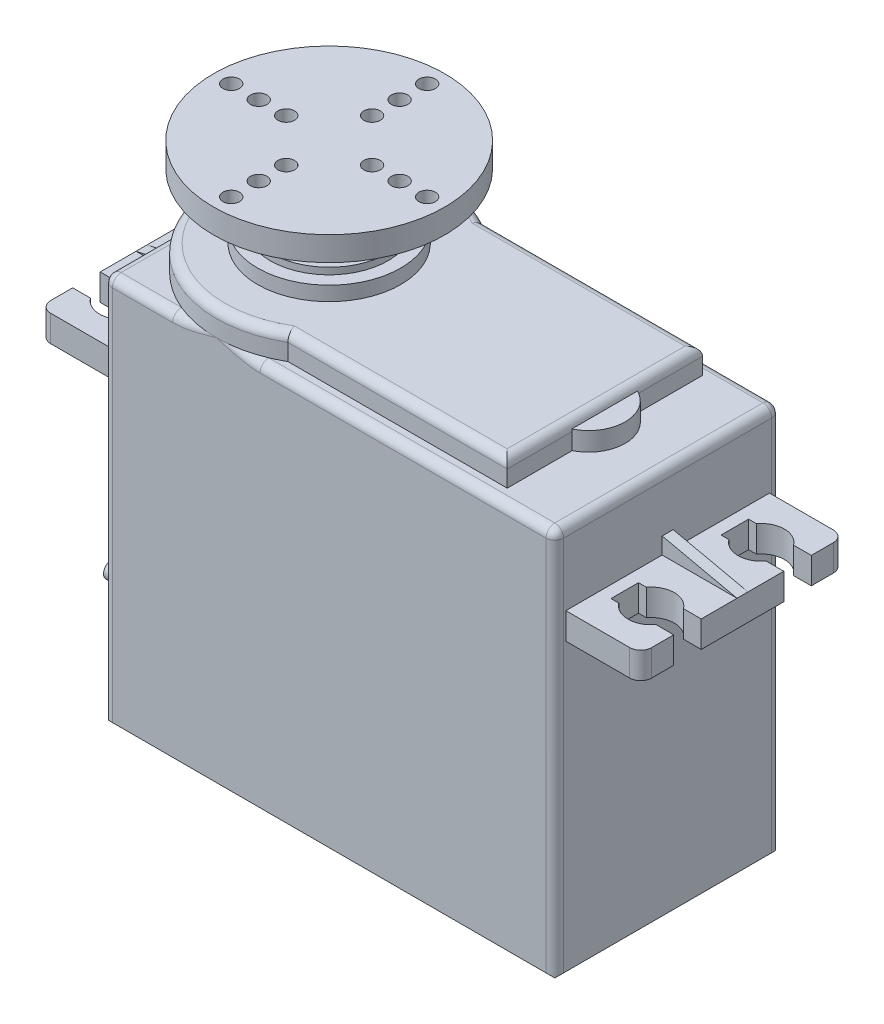
SolidWorks part; units mm, degrees
ref_plane "Front Plane" through (0, 0, 0) normal (0, 0, 1) x (1, 0, 0)
ref_plane "Top Plane" through (0, 0, 0) normal (0, 1, 0) x (1, 0, 0)
ref_plane "Right Plane" through (0, 0, 0) normal (1, 0, 0) x (0, 0, -1)
sketch "Sketch1" plane through (0, 0, 0) normal (0, 1, 0) x (1, 0, 0)
  line L1 (-20.5, 10.25) -> (20.5, 10.25)
  line L2 (-20.5, 10.25) -> (-20.5, -10.25)
  line L3 (-20.5, -10.25) -> (20.5, -10.25)
  line L4 (20.5, 10.25) -> (20.5, -10.25)
  line L5 (-20.5, 10.25) -> (20.5, -10.25) construction
  line L6 (-20.5, -10.25) -> (20.5, 10.25) construction
  point P0 (0, 0)
  dimension "D1" = 41
  dimension "D2" = 20.5
extrude "Boss-Extrude1" add sketch "Sketch1" along normal blind 37
chamfer "Chamfer1" distance 2 angle 45 4 edges at (-20.5, 0, 0) (0, 0, -10.25) (20.5, 0, 0) (0, 0, 10.25)
sketch "Sketch2" plane through (0, 37, 0) normal (0, 1, 0) x (1, 0, 0)
  line L0 (-5.122, 8.875) -> (14.8, 8.875)
  line L1 (14.8, 8.875) -> (14.8, 2.9719)
  line L2 (14.8, -8.875) -> (-5.122, -8.875)
  line L3 (20.5, 0) -> (-24.1898, 0) construction
  line L4 (20.5, -10.25) -> (20.5, 10.25) construction
  line L5 (-20.5, 10.25) -> (-20.5, -10.25) construction
  line L6 (20.5, 10.25) -> (-20.5, 10.25) construction
  line L7 (14.8, -2.9719) -> (14.8, -8.875)
  line L8 (14.8, 2.9719) -> (14.8, -2.9719)
  arc A0 (-5.122, 8.875) -> (-5.122, -8.875) centre (-10.25, 0) ccw
  arc A1 (14.8, -2.9719) -> (14.8, 2.9719) centre (13.32, 0) ccw
  dimension "D2" = 6.64
  dimension "D1" = 17.75
  dimension "D3" = 1.48
  dimension "D4" = 5.7
extrude "Boss-Extrude2" add sketch "Sketch2" along normal blind 2.3 contours L8 L3 A0 L2 L7 | L3 L8 L1 L0 A0 | L3 A1 L8 | A1 L3 L8 region at (-2.3856, 37, -4.4911) region at (-2.3856, 37, 4.4911) region at (15.5569, 37, -1.1714) region at (15.5569, 37, 1.1714)
sketch "Sketch3" plane through (0, 39.3, 0) normal (0, 1, 0) x (1, 0, 0)
  line L0 (14.8, 2.9719) -> (14.8, -2.9719)
  arc A1 (14.8, -2.9719) -> (14.8, 2.9719) centre (13.32, 0) ccw construction
  arc A2 (14.8, -2.9719) -> (14.8, 2.9719) centre (13.32, 0) ccw
extrude "Cut-Extrude1" cut sketch "Sketch3" against normal blind 0.6
sketch "Sketch4" plane through (0, 39.3, 0) normal (0, 1, 0) x (1, 0, 0)
  circle A0 centre (-10.25, 0) radius 6.5
  dimension "D1" = 13
extrude "Boss-Extrude3" add sketch "Sketch4" along normal blind 1.3
sketch "Sketch5" plane through (0, 40.6, 0) normal (0, 1, 0) x (1, 0, 0)
  circle A0 centre (-10.25, 0) radius 5.35
  dimension "D1" = 10.7
extrude "Boss-Extrude4" add sketch "Sketch5" along normal blind 0.6
sketch "Sketch6" plane through (0, 41.2, 0) normal (0, 1, 0) x (1, 0, 0)
  circle A0 centre (-10.25, 0) radius 3
  dimension "D1" = 6
extrude "Boss-Extrude5" add sketch "Sketch6" along normal blind 4
sketch "Sketch7" plane through (0, 45.2, 0) normal (0, 1, 0) x (1, 0, 0)
  circle A0 centre (-10.25, 0) radius 10.5
  dimension "D1" = 21
extrude "Boss-Extrude6" add sketch "Sketch7" along normal blind 2.2
sketch "Sketch8" plane through (0, 47.4, 0) normal (0, 1, 0) x (1, 0, 0)
  line L0 (-19.15, 0) -> (-16.65, 0) construction
  line L1 (-16.65, 0) -> (-14.15, 0) construction
  line L2 (-14.15, 0) -> (-10.25, 0) construction
  circle A0 centre (-14.15, 0) radius 0.75
  circle A1 centre (-16.65, 0) radius 0.75
  circle A2 centre (-19.15, 0) radius 0.75
  point P6 (-10.25, 0)
  dimension "D1" = 1.5
  dimension "D2" = 2.5
  dimension "D3" = 2.5
  dimension "D4" = 3.9
extrude "Cut-Extrude2" cut sketch "Sketch8" against normal blind 2.2
pattern_circular "CirPattern1" count 4 over 360 about axis through (-10.25, 47.4, 0) along (0, -1, 0) of "Cut-Extrude2" reverse direction yes
sketch "Sketch9" plane through (-20.5, 0, 0) normal (-1, 0, 0) x (0, 0, 1)
  line L1 (-3.5, 7.4) -> (3.5, 7.4)
  line L2 (-3.5, 7.4) -> (-3.5, 3.2)
  line L3 (-3.5, 3.2) -> (3.5, 3.2)
  line L4 (3.5, 7.4) -> (3.5, 3.2)
  line L5 (-3.5, 7.4) -> (3.5, 3.2) construction
  line L6 (-3.5, 3.2) -> (3.5, 7.4) construction
  point P0 (0, 5.3)
  dimension "D1" = 4.2
  dimension "D2" = 3.2
  dimension "D3" = 7
extrude "Boss-Extrude7" add sketch "Sketch9" along normal blind 1
sketch "Sketch10" plane through (-21.5, 0, 0) normal (-1, 0, 0) x (0, 0, 1)
  line L9 (3.15, 3.55) -> (3.15, 7.05)
  line L10 (3.15, 7.05) -> (-3.15, 7.05)
  line L11 (-3.15, 7.05) -> (-3.15, 3.55)
  line L12 (-3.15, 3.55) -> (3.15, 3.55)
  line L13 (3.15, 3.55) -> (3.15, 7.05)
  line L14 (3.15, 7.05) -> (-3.15, 7.05)
  line L15 (-3.15, 7.05) -> (-3.15, 3.55)
  line L16 (-3.15, 3.55) -> (3.15, 3.55)
  dimension "D1" = 0.35
extrude "Boss-Extrude9" add sketch "Sketch10" along normal blind 4 draft 5
sketch "Sketch12" plane through (-25.5, 0, 0) normal (-1, 0, 0) x (0, 0, 1)
  line L0 (-2.8, 3.9) -> (2.8, 3.9) construction
  circle A0 centre (0, 5.3) radius 0.75
  circle A1 centre (1.5, 5.3) radius 0.75
  circle A2 centre (-1.5, 5.3) radius 0.75
  point P6 (0, 0)
  dimension "D1" = 1.5
  dimension "D2" = 1.4
  dimension "D3" = 1.4
  dimension "D4" = 1.4
extrude "Boss-Extrude10" add sketch "Sketch12" along normal blind 3 separate body contours A1 | A0 | A2 region at (-25.5, 5.3, 0) region at (-25.5, 5.3, -1.5) region at (-25.5, 5.3, 1.5)
fillet "Fillet1" radius 0.8 4 edges at (20.5, 19.5, 10.25) (20.5, 19.5, -10.25) (-20.5, 19.5, -10.25) (-20.5, 19.5, 10.25)
fillet "Fillet2" radius 0.8 15 edges at (-14.975, 37, 10.25) (-20.2657, 37, 10.0157) (-20.5, 37, 4.725) (-20.5, 37, -4.725) (-20.2657, 37, -10.0157) (-14.975, 37, -10.25) (4.725, 37, -10.25) (20.2657, 37, -10.0157) (20.5, 37, 0) (20.2657, 37, 10.0157) (4.725, 37, 10.25) (4.839, 39.3, -8.875) (14.8, 39.3, 0) (4.839, 39.3, 8.875) (-20.5, 39.3, 0)
sketch "Sketch14" plane through (-20.5, 0, 0) normal (-1, 0, 0) x (0, 0, 1)
  line L0 (9.45, 36.2) -> (3.9699, 36.2) construction
  line L1 (-9.25, 30.4) -> (9.25, 30.4)
  line L2 (-9.25, 30.4) -> (-9.25, 28)
  line L3 (-9.25, 28) -> (9.25, 28)
  line L4 (9.25, 30.4) -> (9.25, 28)
  line L5 (-9.25, 30.4) -> (9.25, 28) construction
  line L6 (-9.25, 28) -> (9.25, 30.4) construction
  line L8 (-10.25, 2) -> (-10.25, 36.2) construction
  point P0 (0, 29.2)
  point P7 (-9.25, 29.2)
  dimension "D1" = 18.5
  dimension "D2" = 2.4
  dimension "D3" = 5.8
  dimension "D4" = 1
extrude "Boss-Extrude11" add sketch "Sketch14" along normal blind 6.8
fillet "Fillet3" radius 1 2 edges at (-27.3, 29.2, -9.25) (-27.3, 29.2, 9.25)
sketch "Sketch15" plane through (0, 30.4, 0) normal (0, 1, 0) x (1, 0, 0)
  line L0 (-27.3, 0) -> (-19.7, 0) construction
  line L1 (-27.3, -8.25) -> (-27.3, 8.25) construction
  line L2 (-25.6875, 3.75) -> (-27.3, 3.75)
  line L3 (-21.6, 3.75) -> (-22.3125, 3.75)
  line L4 (-21.6, 3.75) -> (-21.6, 6.25)
  line L5 (-21.6, 6.25) -> (-22.3125, 6.25)
  line L6 (-27.3, 3.75) -> (-27.3, 6.25)
  line L7 (-21.6, 3.75) -> (-27.3, 6.25) construction
  line L8 (-21.6, 6.25) -> (-27.3, 3.75) construction
  line L9 (-25.6875, 6.25) -> (-27.3, 6.25)
  line L10 (-21.6, -6.25) -> (-27.3, -3.75) construction
  line L11 (-21.6, -3.75) -> (-27.3, -6.25) construction
  line L12 (-25.6875, -6.25) -> (-27.3, -6.25)
  line L13 (-27.3, -3.75) -> (-27.3, -6.25)
  line L14 (-21.6, -6.25) -> (-22.3125, -6.25)
  line L15 (-21.6, -3.75) -> (-21.6, -6.25)
  line L16 (-21.6, -3.75) -> (-22.3125, -3.75)
  line L17 (-25.6875, -3.75) -> (-27.3, -3.75)
  arc A0 (-5.3411, 8.075) -> (-5.3411, -8.075) centre (-10.25, 0) ccw construction
  arc A1 (-25.6875, 3.75) -> (-22.3125, 3.75) centre (-24, 5) ccw
  arc A2 (-22.3125, 6.25) -> (-25.6875, 6.25) centre (-24, 5) ccw
  arc A3 (-22.3125, -6.25) -> (-25.6875, -6.25) centre (-24, -5) cw
  arc A4 (-25.6875, -3.75) -> (-22.3125, -3.75) centre (-24, -5) cw
  point P7 (-24.45, 5)
  point P14 (0, 0)
  point P27 (-24.45, -5)
  dimension "D1" = 4.2
  dimension "D2" = 2.5
  dimension "D3" = 5.7
  dimension "D4" = 3.3
  dimension "D5" = 5
extrude "Cut-Extrude3" cut sketch "Sketch15" against normal blind 6.8
sketch "Sketch18" plane through (0, 0, 0) normal (0, 0, 1) x (1, 0, 0)
  line L0 (-27.3, 30.4) -> (-20.5, 30.4)
  line L1 (-20.5, 30.4) -> (-20.5, 31.9)
  line L2 (-20.5, 2) -> (-20.5, 36.2) construction
  line L3 (-20.5, 31.9) -> (-27.3, 30.4)
  dimension "D1" = 1.5
extrude "Boss-Extrude12" add sketch "Sketch18" along normal mid plane 1
ref_plane "Plane1" through (0, 0, 0) normal (-1, 0, 0) x (0, 0, 1)
mirror "Mirror1" about plane through (0, 0, 0) normal (-1, 0, 0) of "Boss-Extrude12", "Fillet3", "Cut-Extrude3", "Boss-Extrude11"
